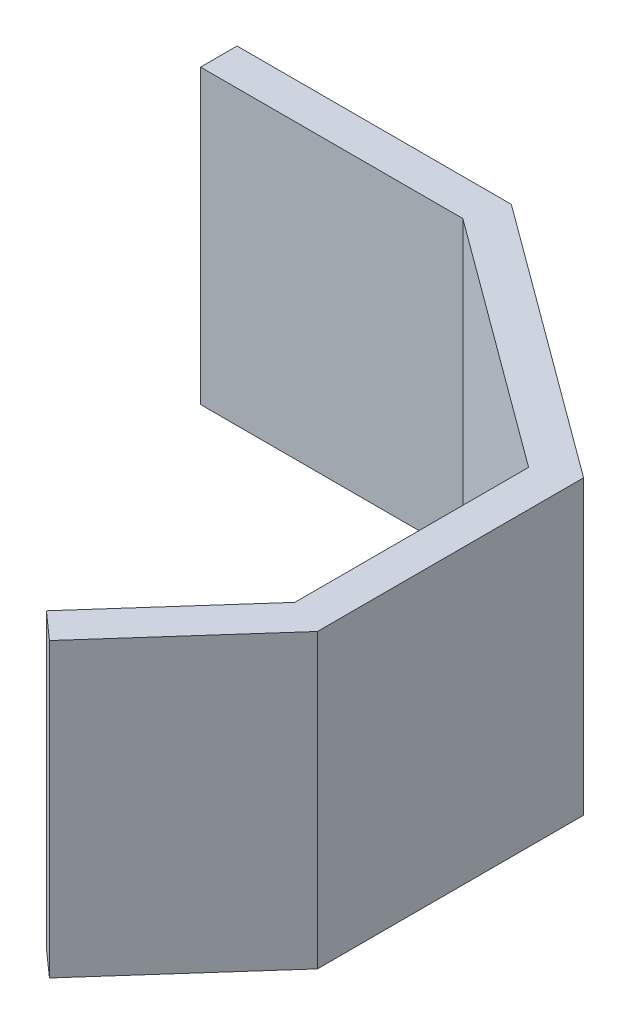
SolidWorks part; units mm, degrees
ref_plane "前视基准面" through (0, 0, 0) normal (0, 0, 1) x (1, 0, 0)
ref_plane "上视基准面" through (0, 0, 0) normal (0, 1, 0) x (1, 0, 0)
ref_plane "右视基准面" through (0, 0, 0) normal (1, 0, 0) x (0, 0, -1)
sketch "草图1" plane through (0, 0, 0) normal (0, 1, 0) x (1, 0, 0)
  line L0 (0, -8) -> (0, 8)
  line L1 (0, 8) -> (-17, 20.5)
  line L2 (0, -8) -> (-8, -17)
  line L3 (2.5, -8.9505) -> (-6.1315, -18.6609)
  line L4 (2.5, -8.9505) -> (2.5, 9.2648)
  line L5 (2.5, 9.2648) -> (-16.1798, 23)
  line L6 (-6.1315, -18.6609) -> (-8, -17)
  line L7 (-17, 20.5) -> (-34.9509, 20.5)
  line L8 (-34.9509, 23) -> (-16.1798, 23)
  line L9 (2.5, 9.2648) -> (-15.519, 22.5141) construction
  line L10 (-34.9509, 23) -> (-34.9509, 20.5)
  dimension "D1" = 16
  dimension "D2" = 12.5
  dimension "D3" = 17
  dimension "D4" = 9
  dimension "D5" = 8
  dimension "D7" = 2.5
  dimension "D6" = 2.5
extrude "凸台-拉伸1" add sketch "草图1" along normal blind 10 and the other way blind 10
